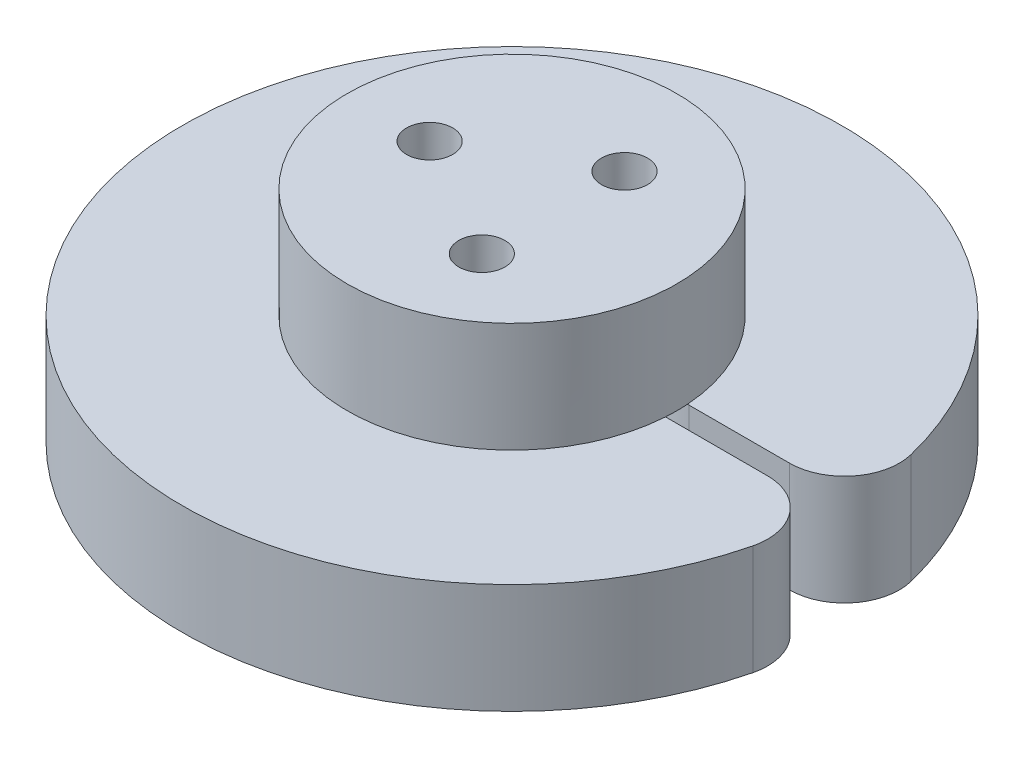
SolidWorks part; units mm, degrees
ref_plane "前视基准面" through (0, 0, 0) normal (0, 0, 1) x (1, 0, 0)
ref_plane "上视基准面" through (0, 0, 0) normal (0, 1, 0) x (1, 0, 0)
ref_plane "右视基准面" through (0, 0, 0) normal (1, 0, 0) x (0, 0, -1)
other "Configuration Table"
sketch "草图1" plane through (0, 0, 0) normal (0, 1, 0) x (1, 0, 0)
  circle A0 centre (0, 0) radius 30
  dimension "D1" = 60
extrude "凸台-拉伸1" add sketch "草图1" along normal blind 10
sketch "草图2" plane through (0, 10, 0) normal (0, 1, 0) x (1, 0, 0)
  circle A0 centre (0, 0) radius 15.01
  dimension "D1" = 30.02
extrude "凸台-拉伸2" add sketch "草图2" along normal blind 10
sketch "草图3" plane through (0, 0, 0) normal (0, -1, 0) x (1, 0, 0)
  circle A0 centre (0, 0) radius 15.025
  dimension "D1" = 30.05
extrude "凸台-拉伸3" add sketch "草图3" along normal blind 6
sketch "草图4" plane through (0, -6, 0) normal (0, -1, 0) x (1, 0, 0)
  circle A0 centre (0, 0) radius 7.5 construction
  circle A1 centre (-7.5, 0) radius 2.1
  circle A2 centre (3.75, 6.4952) radius 2.1
  circle A3 centre (3.75, -6.4952) radius 2.1
  point P11 (0, 0)
  dimension "D1" = 15
  dimension "D2" = 4.2
  dimension "D3" = 3
extrude "切除-拉伸1" cut sketch "草图4" against normal through all
sketch "草图6" plane through (0, 10, 0) normal (0, 1, 0) x (1, 0, 0)
  line L0 (10.9343, 1) -> (10.9343, -1) construction
  line L1 (10.9343, 1) -> (30.9343, 1)
  line L3 (10.9343, -1) -> (30.9343, -1)
  line L4 (30.9343, 1) -> (30.9343, -1)
  arc A0 (10.9343, 1) -> (10.9343, -1) centre (8, 0) ccw
  dimension "D1" = 6.2
  dimension "D2" = 8
  dimension "D3" = 2
  dimension "D4" = 20
extrude "切除-拉伸3" cut sketch "草图6" against normal through all
fillet "圆角1" radius 10 2 edges at (10.9343, 2, -1) (10.9343, 2, 1)
fillet "圆角2" radius 5 2 edges at (29.9833, 5, -1) (29.9833, 5, 1)
fillet "圆角3" radius 0.2 2 edges at (14.9916, -3, 1.0007) (14.9916, -3, -1.0007)
sketch "草图7" plane through (0, 10, 0) normal (0, -1, 0) x (1, 0, 0)
  circle A0 centre (8, 0) radius 1.25
  dimension "D1" = 2.5
extrude "切除-拉伸4" cut sketch "草图7" against normal blind 8
